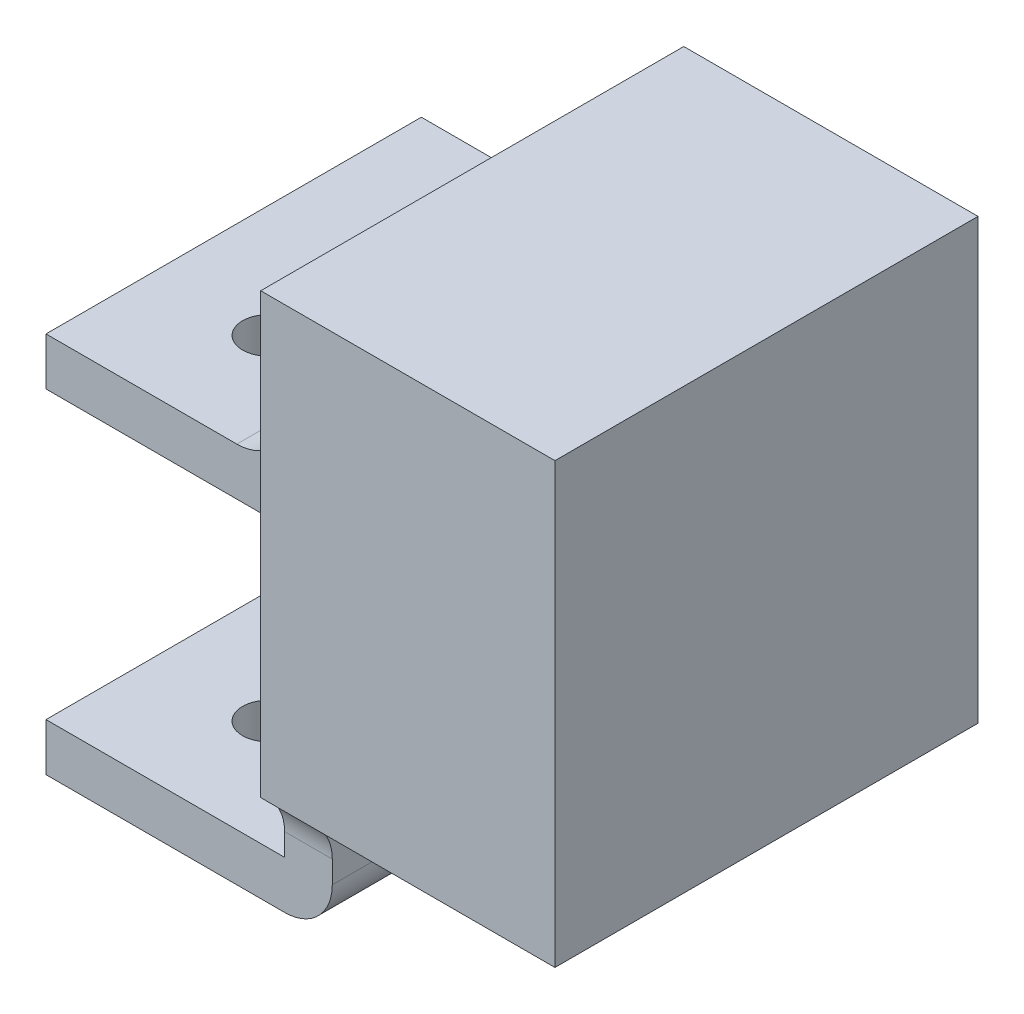
SolidWorks part; units mm, degrees
material "Custom Plastic"
ref_plane "Front Plane" through (0, 0, 0) normal (0, 0, 1) x (1, 0, 0)
ref_plane "Top Plane" through (0, 0, 0) normal (0, 1, 0) x (1, 0, 0)
ref_plane "Right Plane" through (0, 0, 0) normal (1, 0, 0) x (0, 0, -1)
sketch "Sketch1" plane through (0, 0, 0) normal (1, 0, 0) x (0, 0, -1)
  line L1 (-11.8, -12.3) -> (11.8, -12.3)
  line L2 (-11.8, -12.3) -> (-11.8, 12.3)
  line L3 (-11.8, 12.3) -> (11.8, 12.3)
  line L4 (11.8, -12.3) -> (11.8, 12.3)
  line L5 (-11.8, -12.3) -> (11.8, 12.3) construction
  line L6 (-11.8, 12.3) -> (11.8, -12.3) construction
  line L7 (-13.3, -13.8) -> (13.3, -13.8)
  line L8 (-13.3, -13.8) -> (-13.3, 13.8)
  line L9 (-13.3, 13.8) -> (13.3, 13.8)
  line L10 (13.3, -13.8) -> (13.3, 13.8)
  line L11 (-13.3, -13.8) -> (13.3, 13.8) construction
  line L12 (-13.3, 13.8) -> (13.3, -13.8) construction
  point P0 (0, 0)
  point P6 (0, 0)
  dimension "D1" = 24.6
  dimension "D2" = 23.6
  dimension "D3" = 26.6
  dimension "D4" = 24.6
  dimension "D5" = 27.6
extrude "Boss-Extrude1" add sketch "Sketch1" along normal blind 12.5
sketch "Sketch2" plane through (0, 0, 0) normal (-1, 0, 0) x (0, 0, 1)
  line L1 (-13.3, 13.8) -> (13.3, 13.8)
  line L2 (-13.3, 13.8) -> (-13.3, -13.8)
  line L3 (-13.3, -13.8) -> (13.3, -13.8)
  line L4 (13.3, 13.8) -> (13.3, -13.8)
extrude "Boss-Extrude2" add sketch "Sketch2" along normal blind 3
sketch "Sketch3" plane through (0, 0, -13.3) normal (0, 0, -1) x (-1, 0, 0)
sketch "Sketch4" plane through (12.5, 0, 0) normal (1, 0, 0) x (0, 0, -1)
  line L1 (-13.3, 13.8) -> (13.3, 13.8)
  line L2 (-13.3, 13.8) -> (-13.3, -13.8)
  line L3 (-13.3, -13.8) -> (13.3, -13.8)
  line L4 (13.3, 13.8) -> (13.3, -13.8)
extrude "Boss-Extrude3" add sketch "Sketch4" along normal blind 3
sketch "Sketch6" plane through (0, -13.8, 0) normal (0, -1, 0) x (-1, 0, 0)
  line L0 (0, 14.63) -> (0, -14.63) construction
  line L1 (0, -10.3) -> (-12.5, -10.3)
  line L2 (0, -10.3) -> (0, 10.3)
  line L3 (0, 10.3) -> (-12.5, 10.3)
  line L4 (-12.5, -10.3) -> (-12.5, 10.3)
  line L5 (-15.5, -13.3) -> (3, -13.3) construction
  line L6 (3, 13.3) -> (3, -13.3) construction
  line L7 (-15.5, -13.3) -> (-15.5, 13.3) construction
  line L8 (-15.5, 13.3) -> (3, 13.3) construction
  dimension "D1" = 3
  dimension "D2" = 3
  dimension "D3" = 3
  dimension "D4" = 3
extrude "Cut-Extrude1" cut sketch "Sketch6" against normal blind 3
sketch "Sketch7" plane through (0, -13.8, 0) normal (0, -1, 0) x (-1, 0, 0)
  line L0 (1.2891, -13.3) -> (1.2891, -4.9) construction
  line L1 (-15.5, -13.3) -> (3, -13.3) construction
  line L2 (1.2891, -4.9) -> (1.2891, 4.9) construction
  line L3 (1.2891, 4.9) -> (1.2891, 13.3) construction
  line L4 (-15.5, 13.3) -> (3, 13.3) construction
  line L5 (0, 14.63) -> (0, -14.63) construction
  line L6 (0, -7.4191) -> (12.54, -7.4191)
  line L7 (0, -7.4191) -> (0, 6.9729)
  line L8 (0, 6.9729) -> (12.54, 6.9729)
  line L9 (12.54, -7.4191) -> (12.54, 6.9729)
  dimension "D1" = 8.4
  dimension "D2" = 9.8
  dimension "D3" = 8.4
  dimension "D4" = 12.54
extrude "Boss-Extrude4" add sketch "Sketch7" along normal blind 7 and the other way blind 17
sketch "Sketch8" plane through (0, -20.8, 0) normal (0, -1, 0) x (-1, 0, 0)
  line L0 (12.54, 4.9005) -> (12.54, -4.9633)
  circle A0 centre (9.94, -4.9005) radius 1.6
  circle A1 centre (9.94, 4.8367) radius 1.6
  point P3 (12.54, -0.0633)
  point P8 (12.54, 0)
  dimension "D3" = 3.2
  dimension "D4" = 3.2
extrude "Cut-Extrude2" cut sketch "Sketch8" against normal through all contours A0 | A1 region at (-9.94, -20.8, 4.9005) region at (-9.94, -20.8, -4.8367)
sketch "Sketch10" plane through (0, 0, 7.4191) normal (0, 0, 1) x (1, 0, 0)
  line L0 (-12.54, 3.2) -> (-12.54, -20.8) construction
  line L1 (-12.54, 0.2) -> (-3, 0.2)
  line L2 (-12.54, 0.2) -> (-12.54, -17.8)
  line L3 (-12.54, -17.8) -> (-3, -17.8)
  line L4 (-3, 0.2) -> (-3, -17.8)
  line L5 (0, -20.8) -> (-12.54, -20.8) construction
  dimension "D1" = 3
  dimension "D2" = 3
  dimension "D3" = 18
extrude "Cut-Extrude3" cut sketch "Sketch10" against normal through all
sketch "Sketch11" plane through (0, 0, 13.3) normal (0, 0, 1) x (1, 0, 0)
  line L0 (-3, -13.8) -> (-3, 13.8) construction
  line L1 (2, 10.8) -> (7.5, 10.8)
  line L2 (2, 10.8) -> (2, -7.8)
  line L3 (2, -7.8) -> (7.5, -7.8)
  line L4 (7.5, 10.8) -> (7.5, -7.8)
  line L5 (15.5, 13.8) -> (15.5, -13.8) construction
  line L6 (15.5, 13.8) -> (-3, 13.8) construction
  line L7 (15.5, -13.8) -> (-3, -13.8) construction
  dimension "D1" = 5
  dimension "D2" = 8
  dimension "D3" = 3
  dimension "D4" = 6
sketch "Sketch14" plane through (0, -13.8, 0) normal (0, -1, 0) x (-1, 0, 0)
  line L0 (0, 14.63) -> (0, -14.63) construction
  line L1 (-12.5, -11.8) -> (0, -11.8)
  line L2 (-12.5, -11.8) -> (-12.5, 11.8)
  line L3 (-12.5, 11.8) -> (0, 11.8)
  line L4 (0, -11.8) -> (0, 11.8)
  line L5 (-15.5, -13.3) -> (3, -13.3) construction
  line L6 (-15.5, 13.3) -> (3, 13.3) construction
  dimension "D1" = 1.5
  dimension "D2" = 1.5
extrude "Cut-Extrude5" cut sketch "Sketch14" against normal blind 3
sketch "Sketch16" plane through (0, 0, 13.3) normal (0, 0, 1) x (1, 0, 0)
  line L1 (2, 10.8) -> (7.5, 10.8)
  line L2 (2, 10.8) -> (2, -7.8)
  line L3 (2, -7.8) -> (7.5, -7.8)
  line L4 (7.5, 10.8) -> (7.5, -7.8)
sketch "Sketch17" plane through (0, -13.8, 0) normal (0, -1, 0) x (-1, 0, 0)
  line L0 (0, 14.63) -> (0, -14.63) construction
  line L1 (-15.5, -13.3) -> (0, -13.3)
  line L2 (-15.5, -13.3) -> (-15.5, 13.3)
  line L3 (-15.5, 13.3) -> (0, 13.3)
  line L4 (0, -13.3) -> (0, 13.3)
  line L5 (-15.5, 13.3) -> (3, 13.3) construction
sketch "Sketch24" plane through (0, -13.8, 0) normal (0, -1, 0) x (-1, 0, 0)
  line L0 (0, -13.3) -> (0, 13.3) construction
  line L1 (3, -13.3) -> (0, -13.3)
  line L2 (3, -13.3) -> (3, -7.4191)
  line L3 (3, -7.4191) -> (0, -7.4191)
  line L4 (0, -13.3) -> (0, -7.4191)
  line L5 (0, -7.4191) -> (12.54, -7.4191) construction
extrude "Boss-Extrude7" add sketch "Sketch24" along normal blind 7
sketch "Sketch25" plane through (0, -13.8, 0) normal (0, -1, 0) x (-1, 0, 0)
  line L1 (0, 13.3) -> (3, 13.3)
  line L2 (0, 13.3) -> (0, 6.9729)
  line L3 (0, 6.9729) -> (3, 6.9729)
  line L4 (3, 13.3) -> (3, 6.9729)
extrude "Boss-Extrude8" add sketch "Sketch25" along normal blind 7
sketch "Sketch27" plane through (-3, 0, 0) normal (-1, 0, 0) x (0, 0, 1)
  line L0 (-13.3, 13.8) -> (-13.3, -20.8) construction
  line L1 (-13.3, -17.8) -> (13.3, -17.8)
  line L2 (-13.3, -17.8) -> (-13.3, -20.8)
  line L3 (-13.3, -20.8) -> (13.3, -20.8)
  line L4 (13.3, -17.8) -> (13.3, -20.8)
extrude "Boss-Extrude9" add sketch "Sketch27" along normal blind 20
sketch "Sketch29" plane through (0, -17.8, 0) normal (0, 1, 0) x (1, 0, 0)
  line L0 (-9.94, 4.8367) -> (-9.94, -4.9005)
  line L1 (-9.94, 4.8367) -> (-10.64, 4.8367) construction
  dimension "D1" = 0.7
sketch "Sketch30" plane through (0, -17.8, 0) normal (0, 1, 0) x (1, 0, 0)
  line L0 (-10.64, 4.8367) -> (-10.64, -4.9005)
sketch "Sketch32" plane through (-3, 0, 0) normal (-1, 0, 0) x (0, 0, 1)
  line L0 (-13.3, 13.8) -> (-13.3, -17.8) construction
  line L1 (-13.3, 3.2) -> (13.3, 3.2)
  line L2 (-13.3, 3.2) -> (-13.3, 0.2)
  line L3 (-13.3, 0.2) -> (13.3, 0.2)
  line L4 (13.3, 3.2) -> (13.3, 0.2)
  line L5 (13.3, 10.8) -> (13.3, -7.8) construction
extrude "Boss-Extrude10" add sketch "Sketch32" along normal blind 20
fillet "Fillet1" radius 3 1 edges at (0, -20.8, 0)
sketch "Sketch35" plane through (0, 0, 13.3) normal (0, 0, 1) x (1, 0, 0)
  line L1 (-3, 3.2) -> (-23, 3.2)
  line L2 (-3, 3.2) -> (-3, -20.8)
  line L3 (-3, -20.8) -> (-23, -20.8)
  line L4 (-23, 3.2) -> (-23, -20.8)
extrude "Cut-Extrude9" cut sketch "Sketch35" against normal blind 1.5
sketch "Sketch36" plane through (0, 0, 13.3) normal (0, 0, 1) x (1, 0, 0)
  line L0 (-3, -20.8) -> (-3, 13.8) construction
  line L1 (-3, -13.8) -> (0, -13.8)
  line L2 (-3, -13.8) -> (-3, -20.8)
  line L3 (-3, -20.8) -> (0, -20.8)
  line L4 (0, -13.8) -> (0, -20.8)
  line L5 (0, -14.63) -> (0, 14.63) construction
extrude "Cut-Extrude10" cut sketch "Sketch36" against normal blind 1.5
sketch "Sketch37" plane through (0, 0, -13.3) normal (0, 0, -1) x (-1, 0, 0)
  line L1 (23, 3.2) -> (3, 3.2)
  line L2 (23, 3.2) -> (23, -20.8)
  line L3 (23, -20.8) -> (3, -20.8)
  line L4 (3, 3.2) -> (3, -20.8)
extrude "Cut-Extrude11" cut sketch "Sketch37" against normal blind 1.5
sketch "Sketch38" plane through (0, 0, -13.3) normal (0, 0, -1) x (-1, 0, 0)
  line L0 (-15.5, -13.8) -> (0, -13.8) construction
  line L1 (3, -20.8) -> (0, -20.8)
  line L2 (3, -20.8) -> (3, -13.8)
  line L3 (3, -13.8) -> (0, -13.8)
  line L4 (0, -20.8) -> (0, -13.8)
  line L5 (0, 14.63) -> (0, -14.63) construction
extrude "Cut-Extrude12" cut sketch "Sketch38" against normal blind 1.5
fillet "Fillet3" radius 3 1 edges at (-1.5, -13.8, 11.8)
fillet "Fillet4" radius 3 1 edges at (-1.5, -13.8, -11.8)
fillet "Fillet5" radius 3 1 edges at (-3, 3.2, 0)
sketch "Sketch39" plane through (0, -20.8, 0) normal (0, -1, 0) x (-1, 0, 0)
  line L0 (3, 11.8) -> (23, 11.8) construction
  line L1 (23, -11.8) -> (18, -11.8)
  line L2 (23, -11.8) -> (23, 11.8)
  line L3 (23, 11.8) -> (18, 11.8)
  line L4 (18, -11.8) -> (18, 11.8)
  dimension "D1" = 5
extrude "Cut-Extrude13" cut sketch "Sketch39" against normal blind 24
sketch "Sketch40" plane through (0, -17.8, 0) normal (0, 1, 0) x (1, 0, 0)
  line L0 (-10.64, 4.8367) -> (-10.94, 4.8367)
  line L1 (-10.94, 4.8367) -> (-10.94, -4.9005)
  dimension "D1" = 0.3
sketch "Sketch41" plane through (0, -20.8, 0) normal (0, -1, 0) x (-1, 0, 0)
  circle A0 centre (10.94, -4.9005) radius 1.6
  circle A1 centre (10.94, 4.8367) radius 1.6
  dimension "D1" = 3.2
  dimension "D2" = 3.2
extrude "Cut-Extrude14" cut sketch "Sketch41" against normal blind 24
sketch "Sketch42" plane through (0, 0, 11.8) normal (0, 0, -1) x (-1, 0, 0)
  line L1 (-7.5, -7.8) -> (-2, -7.8)
  line L2 (-7.5, -7.8) -> (-7.5, 10.8)
  line L3 (-7.5, 10.8) -> (-2, 10.8)
  line L4 (-2, -7.8) -> (-2, 10.8)
extrude "Cut-Extrude15" cut sketch "Sketch42" along normal through all
